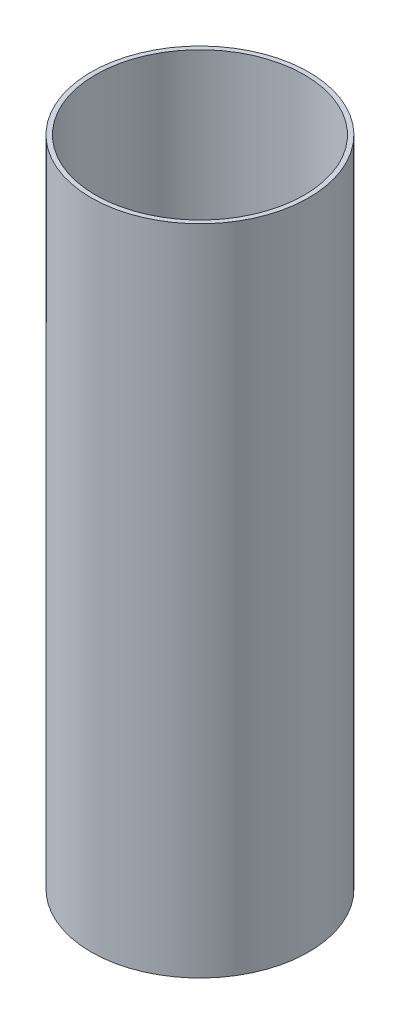
SolidWorks part; units mm, degrees
material "Polycarbonate"
ref_plane "Front Plane" through (0, 0, 0) normal (0, 0, 1) x (1, 0, 0)
ref_plane "Top Plane" through (0, 0, 0) normal (0, 1, 0) x (1, 0, 0)
ref_plane "Right Plane" through (0, 0, 0) normal (1, 0, 0) x (0, 0, -1)
sketch "Sketch2" plane through (0, 0, 0) normal (0, 1, 0) x (1, 0, 0)
  circle A0 centre (0, 0) radius 73.025
  circle A1 centre (0, 0) radius 76.2
  dimension "D1" = 146.05
  dimension "D2" = 152.4
extrude "Boss-Extrude1" add sketch "Sketch2" along normal blind 457.2
